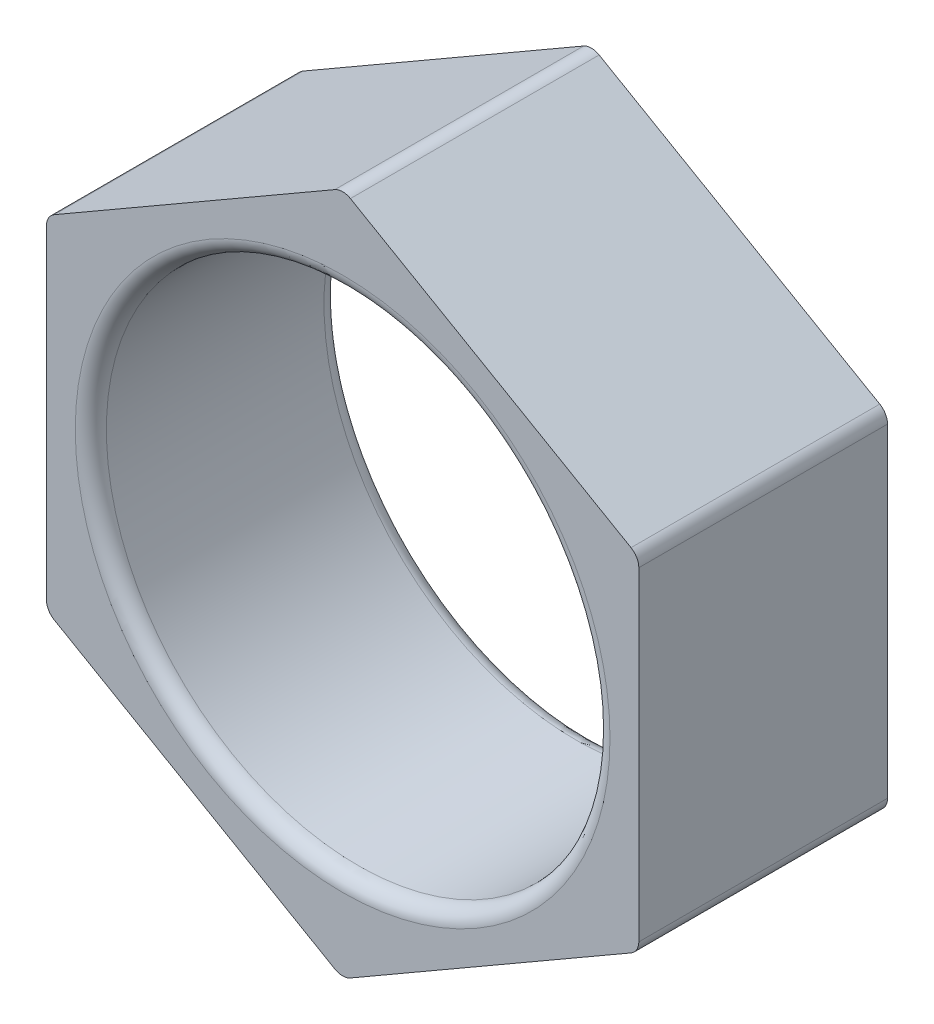
SolidWorks part; units mm, degrees
ref_plane "Front Plane" through (0, 0, 0) normal (0, 0, 1) x (1, 0, 0)
ref_plane "Top Plane" through (0, 0, 0) normal (0, 1, 0) x (1, 0, 0)
ref_plane "Right Plane" through (0, 0, 0) normal (1, 0, 0) x (0, 0, -1)
sketch "Sketch1" plane through (0, 0, 0) normal (0, 0, 1) x (1, 0, 0)
  line L1 (0, 5.5) -> (-4.7631, 2.75)
  line L2 (-4.7631, 2.75) -> (-4.7631, -2.75)
  line L3 (-4.7631, -2.75) -> (0, -5.5)
  line L4 (0, -5.5) -> (4.7631, -2.75)
  line L5 (4.7631, -2.75) -> (4.7631, 2.75)
  line L6 (4.7631, 2.75) -> (0, 5.5)
  circle A0 centre (0, 0) radius 4.7631 construction
  dimension "D1" = 11
extrude "Boss-Extrude1" add sketch "Sketch1" along normal blind 4
sketch "Sketch2" plane through (0, 0, 4) normal (0, 0, 1) x (1, 0, 0)
  circle A0 centre (0, 0) radius 4.05
  dimension "D1" = 8.1
extrude "Cut-Extrude1" cut sketch "Sketch2" against normal through all
fillet "Fillet1" radius 0.25 8 edges at (4.05, 0, 4) (4.05, 0, 0) (-4.7631, 2.75, 2) (-4.7631, -2.75, 2) (0, -5.5, 2) (4.7631, -2.75, 2) (4.7631, 2.75, 2) (0, 5.5, 2)
